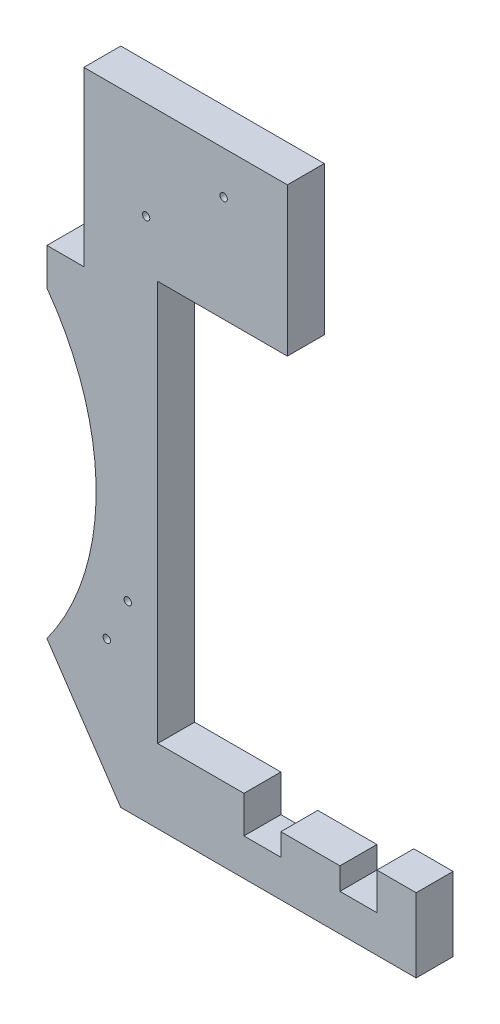
SolidWorks part; units mm, degrees
material "Balsa"
ref_plane "Plan de face" through (0, 0, 0) normal (0, 0, 1) x (1, 0, 0)
ref_plane "Plan de dessus" through (0, 0, 0) normal (0, 1, 0) x (1, 0, 0)
ref_plane "Plan de droite" through (0, 0, 0) normal (1, 0, 0) x (0, 0, -1)
sketch "Esquisse1" plane through (0, 0, 0) normal (0, 0, 1) x (1, 0, 0)
  line L0 (50, 0) -> (50, 10)
  line L1 (10, 0) -> (50, 0)
  line L2 (10, 0) -> (0, 14.8116)
  line L3 (0, 60.9124) -> (5, 60.9124)
  line L4 (50, 10) -> (15, 10)
  line L5 (15, 10) -> (15, 64.2031)
  line L6 (15, 64.2031) -> (32.5611, 64.2031)
  line L7 (5, 60.9124) -> (5, 84.2947)
  line L8 (0, 60.9124) -> (0, 55.9124)
  line L9 (5, 84.2947) -> (32.5611, 84.2947)
  line L10 (32.5611, 84.2947) -> (32.5611, 64.2031)
  arc A0 (0, 14.8116) -> (0, 55.9124) centre (-28.3316, 35.362) ccw
  dimension "D3" = 35
  dimension "D1" = 5
  dimension "D2" = 5
  dimension "D4" = 10
  dimension "D6" = 15
  dimension "D7" = 10
extrude "Boss.-Extru.1" add sketch "Esquisse1" along normal blind 5
sketch "Esquisse3" plane through (0, 0, 0) normal (0, 0, -1) x (-1, 0, 0)
  line L0 (-50, 10) -> (-15, 10) construction
  line L1 (-39.6801, 8) -> (-31.6801, 8)
  line L2 (-44.6801, 10) -> (-44.6801, 5)
  line L3 (-44.6801, 5) -> (-39.6801, 5)
  line L4 (-39.6801, 8) -> (-39.6801, 5)
  line L5 (-50, 0) -> (-50, 10) construction
  line L6 (-31.6801, 5) -> (-26.6801, 5)
  line L7 (-31.6801, 8) -> (-31.6801, 5)
  line L8 (-44.6801, 10) -> (-26.6801, 10)
  line L9 (-26.6801, 5) -> (-26.6801, 10)
  circle A0 centre (-8.1026, 18.8175) radius 0.5
  circle A1 centre (-10.9495, 24.6609) radius 0.5
  circle A2 centre (-23.9301, 78.5447) radius 0.5
  circle A3 centre (-13.4301, 71.0447) radius 0.5
  dimension "D1" = 1
  dimension "D2" = 1
  dimension "D3" = 5
  dimension "D4" = 8
  dimension "D5" = 5
  dimension "D6" = 5.3199
  dimension "D7" = 5
  dimension "D8" = 3
extrude "Enlèv. mat.-Extru.1" cut sketch "Esquisse3" against normal blind 5
